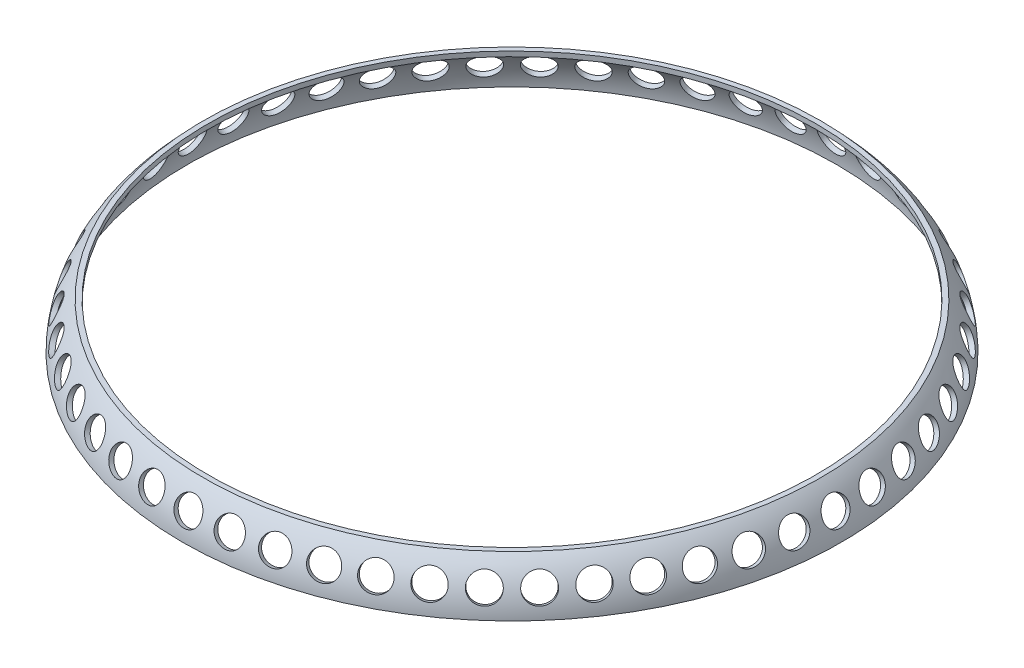
SolidWorks part; units mm, degrees
ref_plane "Front Plane" through (0, 0, 0) normal (0, 0, 1) x (1, 0, 0)
ref_plane "Top Plane" through (0, 0, 0) normal (0, 1, 0) x (1, 0, 0)
ref_plane "Right Plane" through (0, 0, 0) normal (1, 0, 0) x (0, 0, -1)
sketch "Sketch1" plane through (0, 0, 0) normal (0, 0, 1) x (1, 0, 0)
  line L0 (0, 0) -> (0, 16.2154) construction
  line L1 (67.9, 10.2) -> (67.9, 9.1)
  line L2 (0, 0) -> (72.5, 0) construction
  line L3 (73.6, 0) -> (72.5, 0)
  line L4 (67.9, 10.2) -> (69, 10.2)
  line L5 (67.9, 9.1) -> (69, 9.1)
  line L6 (69, 10.2) -> (69, 9.1)
  arc A2 (69, 10.2) -> (73.6, 0) centre (58.6129, -0.6216) cw
  arc A3 (69, 9.1) -> (72.5, 0) centre (57.5098, -0.5424) cw
  dimension "D5" = 15
  dimension "D6" = 15
  dimension "D1" = 10.2
  dimension "D2" = 147.2
  dimension "D3" = 135.8
  dimension "D4" = 1.1
revolve "Revolve1" add sketch "Sketch1" angle 360 about L0 region at (68.45, 9.65, 0) region at (71.7434, 4.7893, 0)
sketch "Sketch2" plane through (0, 0, 0) normal (0, 1, 0) x (1, 0, 0)
  line L0 (0, 73.6) -> (0, -73.6) construction
  circle A0 centre (0, 0) radius 73.6 construction
ref_plane "Plane1" through (0, 0, 0) normal (-0.9397, 0.342, 0) x (0, 0, 1)
sketch "Sketch3" plane through (0, 0, 0) normal (-0.9397, 0.342, 0) x (0, 0, 1)
  line L0 (0, 0) -> (0, -19.6727) construction
  line L1 (0, -19.6727) -> (0, -25.1727) construction
  circle A0 centre (0, -19.6727) radius 3
  ellipse E0 centre (0, 0) end of major axis (-73.6, 0) minor radius 25.1727 construction
  point P3 (0, -22.6727)
  point P5 (0, -25.1727)
  dimension "D1" = 6
  dimension "D2" = 2.5
extrude "Cut-Extrude1" cut sketch "Sketch3" along normal through all
pattern_circular "CirPattern1" count 52 over 360 about axis through (0, 10.2, 0) along (0, -1, 0) of "Cut-Extrude1"
